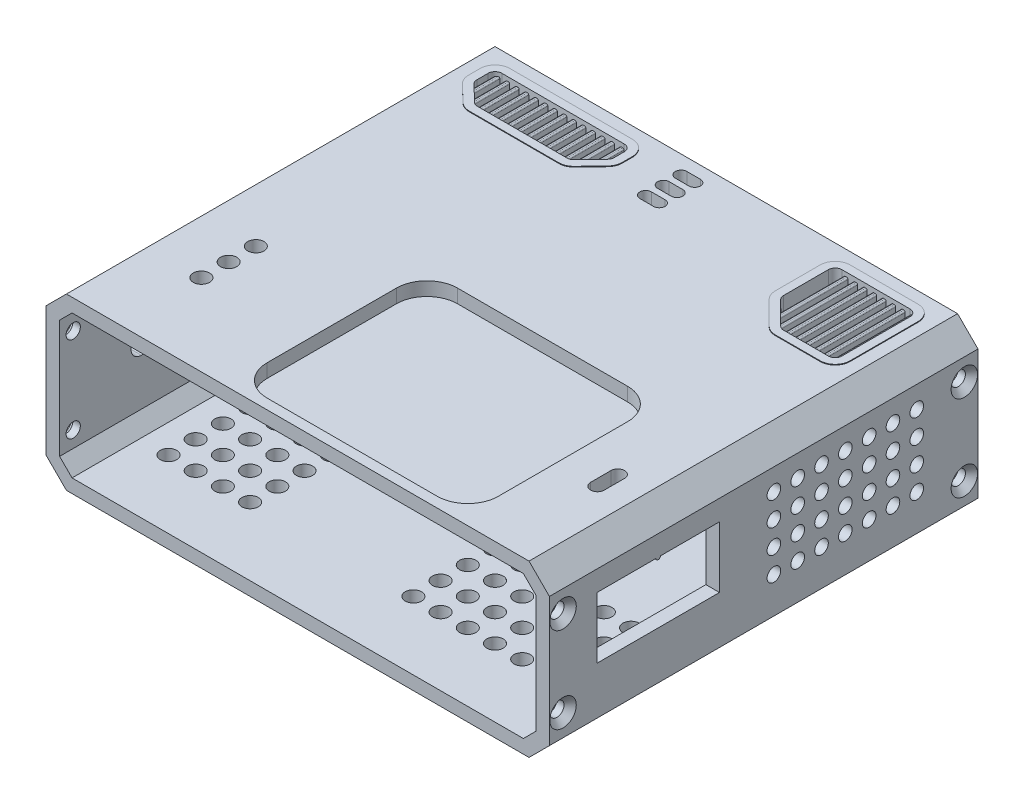
SolidWorks part; units mm, degrees
ref_plane "前视基准面" through (0, 0, 0) normal (0, 0, 1) x (1, 0, 0)
ref_plane "上视基准面" through (0, 0, 0) normal (0, 1, 0) x (1, 0, 0)
ref_plane "右视基准面" through (0, 0, 0) normal (1, 0, 0) x (0, 0, -1)
other "Configuration Table"
sketch "草图1" plane through (0, 0, 0) normal (0, 1, 0) x (1, 0, 0)
  line L1 (-36.9634, 47.435) -> (37.0366, 47.435)
  line L2 (-36.9634, 47.435) -> (-36.9634, -15.565)
  line L3 (-36.9634, -15.565) -> (37.0366, -15.565)
  line L4 (37.0366, 47.435) -> (37.0366, -15.565)
  dimension "D1" = 63
  dimension "D2" = 74
extrude "凸台-拉伸1" add sketch "草图1" along normal blind 25
chamfer "倒角1" distance 3 angle 45 4 edges at (37.0366, 0, -15.935) (-36.9634, 0, -15.935) (-36.9634, 25, -15.935) (37.0366, 25, -15.935)
sketch "草图2" plane through (0, 0, 15.565) normal (0, 0, 1) x (1, 0, 0)
  line L8 (-33.135, 2) -> (33.2082, 2)
  line L9 (35.0366, 3.8284) -> (35.0366, 21.1716)
  line L10 (33.2082, 23) -> (-33.135, 23)
  line L11 (-34.9634, 21.1716) -> (-34.9634, 3.8284)
  line L12 (-33.135, 2) -> (33.2082, 2)
  line L13 (35.0366, 3.8284) -> (35.0366, 21.1716)
  line L14 (33.2082, 23) -> (-33.135, 23)
  line L15 (-34.9634, 21.1716) -> (-34.9634, 3.8284)
  line L16 (33.2082, 2) -> (35.0366, 3.8284)
  line L17 (33.2082, 2) -> (35.0366, 3.8284)
  line L18 (35.0366, 21.1716) -> (33.2082, 23)
  line L19 (35.0366, 21.1716) -> (33.2082, 23)
  line L20 (-33.135, 23) -> (-34.9634, 21.1716)
  line L21 (-33.135, 23) -> (-34.9634, 21.1716)
  line L22 (-34.9634, 3.8284) -> (-33.135, 2)
  line L23 (-34.9634, 3.8284) -> (-33.135, 2)
  dimension "D1" = 2
extrude "切除-拉伸1" cut sketch "草图2" against normal through all
sketch "草图4" plane through (0, 25, 0) normal (0, 1, 0) x (1, 0, 0)
  line L0 (34.0366, 47.435) -> (-33.9634, 47.435) construction
  line L1 (-5.9634, 13.935) -> (19.0366, 13.935)
  line L2 (-10.4634, 9.435) -> (-10.4634, -9.565)
  line L3 (-5.9634, -14.065) -> (19.0366, -14.065)
  line L4 (23.5366, 9.435) -> (23.5366, -9.565)
  line L5 (-33.9634, -15.565) -> (34.0366, -15.565) construction
  line L7 (37.0366, 47.435) -> (37.0366, -15.565) construction
  arc A0 (19.0366, -14.065) -> (23.5366, -9.565) centre (19.0366, -9.565) ccw
  arc A1 (19.0366, 13.935) -> (23.5366, 9.435) centre (19.0366, 9.435) cw
  arc A2 (-10.4634, -9.565) -> (-5.9634, -14.065) centre (-5.9634, -9.565) ccw
  arc A3 (-5.9634, 13.935) -> (-10.4634, 9.435) centre (-5.9634, 9.435) ccw
  point P14 (23.5366, -14.065)
  point P17 (23.5366, 13.935)
  point P22 (-10.4634, 13.935)
  dimension "D5" = 4.5
  dimension "D1" = 34
  dimension "D2" = 1.5
  dimension "D3" = 33.5
  dimension "D4" = 13.5
extrude "切除-拉伸2" cut sketch "草图4" against normal up to next
sketch "草图5" plane through (0, 25, 0) normal (0, 1, 0) x (1, 0, 0)
  line L0 (-36.9634, 0.435) -> (-43.9993, 0.435) construction
  circle A0 centre (-26.1174, 0.435) radius 1.2
  circle A1 centre (-26.1174, 4.435) radius 1.2
  circle A2 centre (-26.1174, -3.565) radius 1.2
  dimension "D3" = 2.4
  dimension "D1" = 4
  dimension "D2" = 4
extrude "切除-拉伸3" cut sketch "草图5" against normal up to next
sketch "草图6" plane through (37.0366, 0, 0) normal (1, 0, 0) x (0, 0, -1)
  line L0 (-15.565, 22) -> (-15.565, 3) construction
  line L1 (-15.565, 3) -> (47.435, 3) construction
  line L2 (47.435, 22) -> (47.435, 3) construction
  line L3 (47.435, 22) -> (-15.565, 22) construction
  circle A0 centre (-13.565, 18.8) radius 1.05
  circle A1 centre (-13.565, 6.2) radius 1.05
  circle A2 centre (45.435, 6.2) radius 1.05
  circle A3 centre (45.435, 18.8) radius 1.05
  dimension "D1" = 2.1
  dimension "D2" = 2
  dimension "D3" = 3.2
  dimension "D4" = 2
  dimension "D5" = 3.2
extrude "切除-拉伸4" cut sketch "草图6" against normal through all
chamfer "倒角2" distance 0.9 angle 45 8 edges at (37.0366, 18.8, -46.485) (37.0366, 6.2, -46.485) (37.0366, 18.8, 12.515) (37.0366, 6.2, 12.515) (-36.9634, 6.2, -46.485) (-36.9634, 18.8, -46.485) (-36.9634, 6.2, 12.515) (-36.9634, 18.8, 12.515)
sketch "草图7" plane through (0, 25, 0) normal (0, 1, 0) x (1, 0, 0)
  line L0 (34.0366, 0.435) -> (47.8552, 0.435) construction
  line L2 (29.5366, 1.9891) -> (29.5366, -1.0109) construction
  line L3 (30.5366, 1.9891) -> (30.5366, -1.0109)
  line L4 (28.5366, 1.9891) -> (28.5366, -1.0109)
  line L5 (37.0366, 47.435) -> (37.0366, -15.565) construction
  arc A0 (30.5366, 1.9891) -> (28.5366, 1.9891) centre (29.5366, 1.9891) ccw
  arc A1 (28.5366, -1.0109) -> (30.5366, -1.0109) centre (29.5366, -1.0109) ccw
  point P3 (29.5366, 0.4891)
  dimension "D3" = 1
  dimension "D1" = 7.5
  dimension "D2" = 3
extrude "切除-拉伸5" cut sketch "草图7" against normal up to next
sketch "草图8" plane through (-36.9634, 0, 0) normal (-1, 0, 0) x (0, 0, 1)
  line L0 (-2.435, 11.4156) -> (-2.435, -8.1835) construction
  line L1 (-8.435, 12.2) -> (3.565, 12.2) construction
  line L2 (-8.435, 13.7) -> (3.565, 13.7)
  line L3 (-8.435, 10.7) -> (3.565, 10.7)
  line L5 (-47.435, 25) -> (15.565, 25) construction
  line L6 (15.565, 22) -> (15.565, 3) construction
  arc A0 (-8.435, 13.7) -> (-8.435, 10.7) centre (-8.435, 12.2) ccw
  arc A1 (3.565, 10.7) -> (3.565, 13.7) centre (3.565, 12.2) ccw
  point P3 (-2.435, 12.2)
  dimension "D4" = 1.5
  dimension "D1" = 18
  dimension "D2" = 12
  dimension "D3" = 12.8
extrude "切除-拉伸6" cut sketch "草图8" against normal up to next
sketch "草图9" plane through (-36.9634, 0, 0) normal (-1, 0, 0) x (0, 0, 1)
  line L1 (-7.435, 7) -> (-3.435, 7)
  line L2 (-7.435, 7) -> (-7.435, 5)
  line L3 (-7.435, 5) -> (-3.435, 5)
  line L4 (-3.435, 7) -> (-3.435, 5)
  line L5 (-47.435, 25) -> (15.565, 25) construction
  line L6 (15.565, 22) -> (15.565, 3) construction
  dimension "D1" = 19
  dimension "D2" = 2
  dimension "D3" = 18
  dimension "D4" = 4
extrude "切除-拉伸7" cut sketch "草图9" against normal up to next
fillet "圆角1" radius 1 4 edges at (-35.9634, 5, -3.435) (-35.9634, 7, -3.435) (-35.9634, 7, -7.435) (-35.9634, 5, -7.435)
sketch "草图10" plane through (-36.9634, 0, 0) normal (-1, 0, 0) x (0, 0, 1)
  line L0 (-47.435, 25) -> (15.565, 25) construction
  line L3 (15.565, 22) -> (15.565, 3) construction
  circle A0 centre (6.465, 19) radius 1
  circle A1 centre (3.265, 19) radius 1
  circle A2 centre (0.065, 19) radius 1
  circle A3 centre (-3.135, 19) radius 1
  circle A4 centre (-6.335, 19) radius 1
  circle A5 centre (3.265, 15.8) radius 1
  circle A6 centre (0.065, 15.8) radius 1
  circle A7 centre (-3.135, 15.8) radius 1
  circle A8 centre (-6.335, 15.8) radius 1
  circle A9 centre (6.465, 15.8) radius 1
  circle A10 centre (-9.535, 19) radius 1
  circle A11 centre (-12.735, 19) radius 1
  circle A12 centre (-15.935, 19) radius 1
  circle A13 centre (-19.135, 19) radius 1
  circle A14 centre (-22.335, 19) radius 1
  circle A15 centre (-25.535, 19) radius 1
  circle A16 centre (-28.735, 19) radius 1
  circle A17 centre (-31.935, 19) radius 1
  circle A18 centre (-35.135, 19) radius 1
  circle A19 centre (-38.335, 19) radius 1
  circle A20 centre (-9.535, 15.8) radius 1
  circle A21 centre (-12.735, 15.8) radius 1
  circle A22 centre (-15.935, 15.8) radius 1
  circle A23 centre (-19.135, 15.8) radius 1
  circle A24 centre (-22.335, 15.8) radius 1
  circle A25 centre (-25.535, 15.8) radius 1
  circle A26 centre (-28.735, 15.8) radius 1
  circle A27 centre (-31.935, 15.8) radius 1
  circle A28 centre (-35.135, 15.8) radius 1
  circle A29 centre (-38.335, 15.8) radius 1
  dimension "D3" = 2
  dimension "D1" = 6
  dimension "D2" = 9.1
  dimension "D4" = 15
  dimension "D5" = 2
extrude "切除-拉伸8" cut sketch "草图10" against normal up to next (2 mm away)
sketch "草图11" plane through (37.0366, 0, 0) normal (1, 0, 0) x (0, 0, -1)
  line L1 (-8.565, 19) -> (9.435, 19)
  line L3 (-8.565, 10) -> (9.435, 10)
  line L5 (-15.565, 25) -> (47.435, 25) construction
  line L18 (-8.565, 19) -> (-8.565, 10)
  line L19 (9.435, 19) -> (9.435, 10)
  line L20 (-15.565, 22) -> (-15.565, 3) construction
  dimension "D1" = 18
  dimension "D2" = 7
  dimension "D3" = 6
  dimension "D4" = 9
extrude "切除-拉伸9" cut sketch "草图11" against normal up to next
sketch "草图12" plane through (0, 0, -47.435) normal (0, 0, -1) x (-1, 0, 0)
  line L0 (-33.2082, 23) -> (33.135, 23) construction
  line L1 (24.9634, 23) -> (26.9634, 23)
  line L2 (24.9634, 23) -> (24.9634, 15.7)
  line L3 (24.9634, 15.7) -> (26.9634, 15.7)
  line L4 (26.9634, 23) -> (26.9634, 15.7)
  line L5 (36.9634, 22) -> (36.9634, 3) construction
  line L6 (-17.0366, 23) -> (-15.0366, 23)
  line L7 (-17.0366, 23) -> (-17.0366, 15.7)
  line L8 (-17.0366, 15.7) -> (-15.0366, 15.7)
  line L9 (-15.0366, 23) -> (-15.0366, 15.7)
  line L10 (-37.0366, 22) -> (-37.0366, 3) construction
  dimension "D1" = 2
  dimension "D2" = 10
  dimension "D3" = 20
  dimension "D4" = 7.3
extrude "凸台-拉伸2" add sketch "草图12" against normal blind 20
chamfer "倒角3" distance 6 angle 45 2 edges at (16.0366, 15.7, -27.435) (-25.9634, 15.7, -27.435)
sketch "草图13" plane through (0, 0, -47.435) normal (0, 0, -1) x (-1, 0, 0)
  line L0 (24.9634, 15.7) -> (26.9634, 15.7) construction
  line L1 (-33.2082, 23) -> (33.135, 23)
  line L2 (-33.2082, 23) -> (-33.2082, 15.7)
  line L3 (-33.2082, 15.7) -> (33.135, 15.7)
  line L4 (33.135, 23) -> (33.135, 15.7)
extrude "切除-拉伸10" cut sketch "草图13" against normal blind 10
sketch "草图15" plane through (37.0366, 0, 0) normal (1, 0, 0) x (0, 0, -1)
  line L0 (-15.565, 25) -> (47.435, 25) construction
  line L1 (47.435, 25) -> (47.435, 22) construction
  circle A0 centre (38.435, 18.8) radius 1
  circle A1 centre (34.935, 18.8) radius 1
  circle A2 centre (31.435, 18.8) radius 1
  circle A3 centre (27.935, 18.8) radius 1
  circle A4 centre (24.435, 18.8) radius 1
  circle A5 centre (20.935, 18.8) radius 1
  circle A6 centre (17.435, 18.8) radius 1
  circle A7 centre (34.935, 15.3) radius 1
  circle A8 centre (31.435, 15.3) radius 1
  circle A9 centre (27.935, 15.3) radius 1
  circle A10 centre (24.435, 15.3) radius 1
  circle A11 centre (20.935, 15.3) radius 1
  circle A12 centre (17.435, 15.3) radius 1
  circle A13 centre (34.935, 11.8) radius 1
  circle A14 centre (31.435, 11.8) radius 1
  circle A15 centre (27.935, 11.8) radius 1
  circle A16 centre (24.435, 11.8) radius 1
  circle A17 centre (20.935, 11.8) radius 1
  circle A18 centre (17.435, 11.8) radius 1
  circle A19 centre (34.935, 8.3) radius 1
  circle A20 centre (31.435, 8.3) radius 1
  circle A21 centre (27.935, 8.3) radius 1
  circle A22 centre (24.435, 8.3) radius 1
  circle A23 centre (20.935, 8.3) radius 1
  circle A24 centre (17.435, 8.3) radius 1
  circle A25 centre (38.435, 15.3) radius 1
  circle A26 centre (38.435, 11.8) radius 1
  circle A27 centre (38.435, 8.3) radius 1
  dimension "D1" = 2
  dimension "D4" = 7
  dimension "D2" = 6.2
  dimension "D3" = 9
  dimension "D5" = 4
extrude "切除-拉伸12" cut sketch "草图15" against normal up to next (2 mm away)
sketch "草图16" plane through (0, 23, 0) normal (0, -1, 0) x (1, 0, 0)
  line L1 (-28.599, -18.535) -> (-26.599, -18.535)
  line L2 (-28.599, -18.535) -> (-28.599, -15.535)
  line L3 (-28.599, -15.535) -> (-26.599, -15.535)
  line L4 (-26.599, -18.535) -> (-26.599, -15.535)
  line L5 (33.2082, -47.435) -> (-33.135, -47.435) construction
  line L6 (26.6682, -18.535) -> (28.6682, -18.535)
  line L7 (26.6682, -18.535) -> (26.6682, -15.535)
  line L8 (26.6682, -15.535) -> (28.6682, -15.535)
  line L9 (28.6682, -18.535) -> (28.6682, -15.535)
  line L10 (-33.135, -47.435) -> (-33.135, 15.565) construction
  line L11 (33.2082, -47.435) -> (33.2082, 15.565) construction
  point P4 (0, 0)
  point P10 (0, 0)
  point P11 (0, 0)
  point P12 (0, 0)
  point P18 (0, 0)
  dimension "D1" = 31.9
  dimension "D2" = 4.5359
  dimension "D3" = 4.54
  dimension "D4" = 2
  dimension "D5" = 3
extrude "凸台-拉伸3" add sketch "草图16" along normal blind 4
sketch "草图18" plane through (0, 2, 0) normal (0, 1, 0) x (1, 0, 0)
  line L0 (33.6224, 49.435) -> (-33.5492, 49.435) construction
  line L1 (37.0366, -15.565) -> (37.0366, 47.435) construction
  line L2 (37.0366, 43.485) -> (37.0366, 47.385) construction
  circle A0 centre (27.0366, 6.435) radius 1.2
  circle A1 centre (23.0366, 6.435) radius 1.2
  circle A2 centre (19.0366, 6.435) radius 1.2
  circle A3 centre (15.0366, 6.435) radius 1.2
  circle A4 centre (11.0366, 6.435) radius 1.2
  circle A5 centre (7.0366, 6.435) radius 1.2
  circle A6 centre (23.0366, 2.435) radius 1.2
  circle A7 centre (19.0366, 2.435) radius 1.2
  circle A8 centre (15.0366, 2.435) radius 1.2
  circle A9 centre (11.0366, 2.435) radius 1.2
  circle A10 centre (7.0366, 2.435) radius 1.2
  circle A11 centre (23.0366, -1.565) radius 1.2
  circle A12 centre (19.0366, -1.565) radius 1.2
  circle A13 centre (15.0366, -1.565) radius 1.2
  circle A14 centre (11.0366, -1.565) radius 1.2
  circle A15 centre (7.0366, -1.565) radius 1.2
  circle A16 centre (23.0366, -5.565) radius 1.2
  circle A17 centre (19.0366, -5.565) radius 1.2
  circle A18 centre (15.0366, -5.565) radius 1.2
  circle A19 centre (11.0366, -5.565) radius 1.2
  circle A20 centre (7.0366, -5.565) radius 1.2
  circle A26 centre (27.0366, 2.435) radius 1.2
  circle A27 centre (27.0366, -1.565) radius 1.2
  circle A28 centre (27.0366, -5.565) radius 1.2
  circle A30 centre (-16.9634, 6.435) radius 1.2
  circle A31 centre (-20.9634, 6.435) radius 1.2
  circle A32 centre (-24.9634, 6.435) radius 1.2
  circle A33 centre (-20.9634, 2.435) radius 1.2
  circle A34 centre (-24.9634, 2.435) radius 1.2
  circle A35 centre (-20.9634, -1.565) radius 1.2
  circle A36 centre (-24.9634, -1.565) radius 1.2
  circle A37 centre (-20.9634, -5.565) radius 1.2
  circle A38 centre (-24.9634, -5.565) radius 1.2
  circle A41 centre (-16.9634, 2.435) radius 1.2
  circle A42 centre (-16.9634, -1.565) radius 1.2
  circle A43 centre (-16.9634, -5.565) radius 1.2
  circle A45 centre (-28.9634, 6.435) radius 1.2
  circle A46 centre (-28.9634, 2.435) radius 1.2
  circle A47 centre (-28.9634, -1.565) radius 1.2
  circle A48 centre (-28.9634, -5.565) radius 1.2
  dimension "D3" = 2.4
  dimension "D1" = 43
  dimension "D2" = 10
  dimension "D6" = 54
  dimension "D4" = 6
  dimension "D5" = 4
  dimension "D7" = 4
  dimension "D8" = 4
extrude "切除-拉伸13" cut sketch "草图18" against normal through all
sketch "草图19" plane through (37.0366, 0, 0) normal (1, 0, 0) x (0, 0, -1)
  line L0 (9.435, 19) -> (-8.565, 19) construction
  circle A0 centre (0.435, 19) radius 0.325
  dimension "D1" = 0.65
extrude "凸台-拉伸4" add sketch "草图19" against normal blind 2
sketch "草图21" plane through (0, 25, 0) normal (0, 1, 0) x (1, 0, 0)
  line L1 (31.0366, 43.435) -> (31.0366, 33.435)
  line L2 (30.0366, 32.435) -> (23.4508, 32.435)
  line L3 (22.7437, 32.7279) -> (19.3295, 36.1421)
  line L4 (19.0366, 36.8492) -> (19.0366, 43.435)
  line L5 (20.0366, 44.435) -> (30.0366, 44.435)
  line L6 (-11.9634, 44.435) -> (-29.9634, 44.435)
  line L7 (-30.9634, 43.435) -> (-30.9634, 41.7558)
  line L8 (-30.6564, 41.0349) -> (-28.2421, 38.7141)
  line L9 (-27.5491, 38.435) -> (-14.3776, 38.435)
  line L10 (-13.6567, 38.742) -> (-11.2425, 41.2535)
  line L11 (-10.9634, 41.9465) -> (-10.9634, 43.435)
  line L12 (34.0366, 47.435) -> (-33.9634, 47.435) construction
  line L13 (34.0366, -15.565) -> (34.0366, 47.435) construction
  line L14 (-33.9634, 47.435) -> (-33.9634, -15.565) construction
  line L26 (-11.9634, 45.635) -> (-29.9634, 45.635)
  line L27 (-32.1634, 43.435) -> (-32.1634, 41.7558)
  line L28 (-31.488, 40.1697) -> (-29.0737, 37.849)
  line L29 (-27.5491, 37.235) -> (-14.3776, 37.235)
  line L30 (-12.7916, 37.9104) -> (-10.3773, 40.4219)
  line L31 (-9.7634, 41.9465) -> (-9.7634, 43.435)
  line L32 (32.2366, 43.435) -> (32.2366, 33.435)
  line L33 (30.0366, 31.235) -> (23.4508, 31.235)
  line L34 (21.8952, 31.8794) -> (18.481, 35.2936)
  line L35 (17.8366, 36.8492) -> (17.8366, 43.435)
  line L36 (20.0366, 45.635) -> (30.0366, 45.635)
  arc A0 (31.0366, 43.435) -> (30.0366, 44.435) centre (30.0366, 43.435) ccw
  arc A1 (31.0366, 33.435) -> (30.0366, 32.435) centre (30.0366, 33.435) cw
  arc A2 (23.4508, 32.435) -> (22.7437, 32.7279) centre (23.4508, 33.435) cw
  arc A3 (19.3295, 36.1421) -> (19.0366, 36.8492) centre (20.0366, 36.8492) cw
  arc A4 (19.0366, 43.435) -> (20.0366, 44.435) centre (20.0366, 43.435) cw
  arc A5 (-14.3776, 38.435) -> (-13.6567, 38.742) centre (-14.3776, 39.435) ccw
  arc A6 (-28.2421, 38.7141) -> (-27.5491, 38.435) centre (-27.5491, 39.435) ccw
  arc A7 (-30.9634, 41.7558) -> (-30.6564, 41.0349) centre (-29.9634, 41.7558) ccw
  arc A8 (-11.2425, 41.2535) -> (-10.9634, 41.9465) centre (-11.9634, 41.9465) ccw
  arc A9 (-10.9634, 43.435) -> (-11.9634, 44.435) centre (-11.9634, 43.435) ccw
  arc A10 (-29.9634, 44.435) -> (-30.9634, 43.435) centre (-29.9634, 43.435) ccw
  arc A11 (-29.9634, 45.635) -> (-32.1634, 43.435) centre (-29.9634, 43.435) ccw
  arc A12 (-32.1634, 41.7558) -> (-31.488, 40.1697) centre (-29.9634, 41.7558) ccw
  arc A13 (-29.0737, 37.849) -> (-27.5491, 37.235) centre (-27.5491, 39.435) ccw
  arc A14 (-14.3776, 37.235) -> (-12.7916, 37.9104) centre (-14.3776, 39.435) ccw
  arc A15 (-10.3773, 40.4219) -> (-9.7634, 41.9465) centre (-11.9634, 41.9465) ccw
  arc A16 (-9.7634, 43.435) -> (-11.9634, 45.635) centre (-11.9634, 43.435) ccw
  arc A17 (32.2366, 33.435) -> (30.0366, 31.235) centre (30.0366, 33.435) cw
  arc A18 (23.4508, 31.235) -> (21.8952, 31.8794) centre (23.4508, 33.435) cw
  arc A19 (18.481, 35.2936) -> (17.8366, 36.8492) centre (20.0366, 36.8492) cw
  arc A20 (17.8366, 43.435) -> (20.0366, 45.635) centre (20.0366, 43.435) cw
  arc A21 (32.2366, 43.435) -> (30.0366, 45.635) centre (30.0366, 43.435) ccw
  point P4 (0, 0)
  point P12 (0, 0)
  point P13 (0, 0)
  point P14 (0, 0)
  point P21 (-20.9634, 38.435)
  point P22 (-20.9634, 44.435)
  point P25 (31.0366, 44.435)
  point P28 (31.0366, 32.435)
  point P31 (23.0366, 32.435)
  point P34 (19.0366, 36.435)
  point P37 (19.0366, 44.435)
  point P40 (-13.9518, 38.435)
  point P43 (-27.9518, 38.435)
  point P50 (-10.9634, 44.435)
  point P53 (-30.9634, 44.435)
  dimension "D11" = 1
  dimension "D1" = 3
  dimension "D2" = 3
  dimension "D3" = 3
  dimension "D4" = 20
  dimension "D5" = 12
  dimension "D6" = 12
  dimension "D7" = 8
  dimension "D8" = 8
  dimension "D9" = 14
  dimension "D10" = 6
  dimension "D12" = 1.2
  dimension "D13" = 1.2
extrude "凸台-拉伸5" add sketch "草图21" along normal blind 0.1
sketch "草图22" plane through (0, 25, 0) normal (0, 1, 0) x (1, 0, 0)
  line L22 (-13.6567, 38.742) -> (-11.2425, 41.2535) construction
  line L23 (-10.9634, 41.9465) -> (-10.9634, 43.435) construction
  line L24 (-11.9634, 44.435) -> (-29.9634, 44.435) construction
  line L25 (-30.9634, 43.435) -> (-30.9634, 41.7558) construction
  line L26 (-30.6564, 41.0349) -> (-28.2421, 38.7141) construction
  line L27 (-27.5491, 38.435) -> (-14.3776, 38.435) construction
  line L28 (30.0366, 44.435) -> (20.0366, 44.435) construction
  line L29 (19.0366, 43.435) -> (19.0366, 36.8492) construction
  line L30 (19.3295, 36.1421) -> (22.7437, 32.7279) construction
  line L31 (23.4508, 32.435) -> (30.0366, 32.435) construction
  line L32 (31.0366, 33.435) -> (31.0366, 43.435) construction
  line L33 (-13.6567, 38.742) -> (-11.2425, 41.2535)
  line L34 (-10.9634, 41.9465) -> (-10.9634, 43.435)
  line L35 (-11.9634, 44.435) -> (-29.9634, 44.435)
  line L36 (-30.9634, 43.435) -> (-30.9634, 41.7558)
  line L37 (-30.6564, 41.0349) -> (-28.2421, 38.7141)
  line L38 (-27.5491, 38.435) -> (-14.3776, 38.435)
  line L39 (30.0366, 44.435) -> (20.0366, 44.435)
  line L40 (19.0366, 43.435) -> (19.0366, 36.8492)
  line L41 (19.3295, 36.1421) -> (22.7437, 32.7279)
  line L42 (23.4508, 32.435) -> (30.0366, 32.435)
  line L43 (31.0366, 33.435) -> (31.0366, 43.435)
  arc A0 (-14.3776, 38.435) -> (-13.6567, 38.742) centre (-14.3776, 39.435) ccw construction
  arc A1 (-11.2425, 41.2535) -> (-10.9634, 41.9465) centre (-11.9634, 41.9465) ccw construction
  arc A2 (-10.9634, 43.435) -> (-11.9634, 44.435) centre (-11.9634, 43.435) ccw construction
  arc A3 (-29.9634, 44.435) -> (-30.9634, 43.435) centre (-29.9634, 43.435) ccw construction
  arc A4 (-30.9634, 41.7558) -> (-30.6564, 41.0349) centre (-29.9634, 41.7558) ccw construction
  arc A5 (-28.2421, 38.7141) -> (-27.5491, 38.435) centre (-27.5491, 39.435) ccw construction
  arc A6 (31.0366, 43.435) -> (30.0366, 44.435) centre (30.0366, 43.435) ccw construction
  arc A7 (20.0366, 44.435) -> (19.0366, 43.435) centre (20.0366, 43.435) ccw construction
  arc A8 (19.0366, 36.8492) -> (19.3295, 36.1421) centre (20.0366, 36.8492) ccw construction
  arc A9 (22.7437, 32.7279) -> (23.4508, 32.435) centre (23.4508, 33.435) ccw construction
  arc A10 (30.0366, 32.435) -> (31.0366, 33.435) centre (30.0366, 33.435) ccw construction
  arc A11 (-14.3776, 38.435) -> (-13.6567, 38.742) centre (-14.3776, 39.435) ccw
  arc A12 (-11.2425, 41.2535) -> (-10.9634, 41.9465) centre (-11.9634, 41.9465) ccw
  arc A13 (-10.9634, 43.435) -> (-11.9634, 44.435) centre (-11.9634, 43.435) ccw
  arc A14 (-29.9634, 44.435) -> (-30.9634, 43.435) centre (-29.9634, 43.435) ccw
  arc A15 (-30.9634, 41.7558) -> (-30.6564, 41.0349) centre (-29.9634, 41.7558) ccw
  arc A16 (-28.2421, 38.7141) -> (-27.5491, 38.435) centre (-27.5491, 39.435) ccw
  arc A17 (31.0366, 43.435) -> (30.0366, 44.435) centre (30.0366, 43.435) ccw
  arc A18 (20.0366, 44.435) -> (19.0366, 43.435) centre (20.0366, 43.435) ccw
  arc A19 (19.0366, 36.8492) -> (19.3295, 36.1421) centre (20.0366, 36.8492) ccw
  arc A20 (22.7437, 32.7279) -> (23.4508, 32.435) centre (23.4508, 33.435) ccw
  arc A21 (30.0366, 32.435) -> (31.0366, 33.435) centre (30.0366, 33.435) ccw
extrude "切除-拉伸15" cut sketch "草图22" against normal blind 2
ref_plane "基准面1" through (0, 24.5, 0) normal (0, 1, 0) x (1, 0, 0)
sketch "草图23" plane through (0, 24.5, 0) normal (0, 1, 0) x (1, 0, 0)
  line L0 (28.7385, 45.7265) -> (29.3385, 45.7265)
  line L1 (30.1385, 45.7265) -> (30.7385, 45.7265)
  line L2 (30.1385, 45.7265) -> (30.1385, 32.4528)
  line L3 (30.1385, 32.4528) -> (30.7385, 32.4528)
  line L4 (30.7385, 45.7265) -> (30.7385, 32.4528)
  line L5 (28.7385, 45.7265) -> (28.7385, 32.4528)
  line L6 (28.7385, 32.4528) -> (29.3385, 32.4528)
  line L7 (29.3385, 45.7265) -> (29.3385, 32.4528)
  line L8 (27.3385, 45.7265) -> (27.9385, 45.7265)
  line L9 (27.3385, 45.7265) -> (27.3385, 32.4528)
  line L10 (27.3385, 32.4528) -> (27.9385, 32.4528)
  line L11 (27.9385, 45.7265) -> (27.9385, 32.4528)
  line L12 (25.9385, 45.7265) -> (26.5385, 45.7265)
  line L13 (25.9385, 45.7265) -> (25.9385, 32.4528)
  line L14 (25.9385, 32.4528) -> (26.5385, 32.4528)
  line L15 (26.5385, 45.7265) -> (26.5385, 32.4528)
  line L16 (24.5385, 45.7265) -> (25.1385, 45.7265)
  line L17 (24.5385, 45.7265) -> (24.5385, 32.4528)
  line L18 (24.5385, 32.4528) -> (25.1385, 32.4528)
  line L19 (25.1385, 45.7265) -> (25.1385, 32.4528)
  line L20 (23.1385, 45.7265) -> (23.7385, 45.7265)
  line L21 (23.1385, 45.7265) -> (23.1385, 32.4528)
  line L22 (23.1385, 32.4528) -> (23.7385, 32.4528)
  line L23 (23.7385, 45.7265) -> (23.7385, 32.4528)
  line L24 (21.7385, 45.7265) -> (22.3385, 45.7265)
  line L25 (21.7385, 45.7265) -> (21.7385, 32.4528)
  line L26 (21.7385, 32.4528) -> (22.3385, 32.4528)
  line L27 (22.3385, 45.7265) -> (22.3385, 32.4528)
  line L28 (20.3385, 45.7265) -> (20.9385, 45.7265)
  line L29 (20.3385, 45.7265) -> (20.3385, 32.4528)
  line L30 (20.3385, 32.4528) -> (20.9385, 32.4528)
  line L31 (20.9385, 45.7265) -> (20.9385, 32.4528)
  line L32 (-13.9994, 46.4523) -> (-13.3994, 46.4523)
  line L33 (-12.5994, 46.4523) -> (-11.9994, 46.4523)
  line L34 (-12.5994, 46.4523) -> (-12.5994, 37.7287)
  line L35 (-12.5994, 37.7287) -> (-11.9994, 37.7287)
  line L36 (-11.9994, 46.4523) -> (-11.9994, 37.7287)
  line L37 (-13.9994, 46.4523) -> (-13.9994, 37.7287)
  line L38 (-13.9994, 37.7287) -> (-13.3994, 37.7287)
  line L39 (-13.3994, 46.4523) -> (-13.3994, 37.7287)
  line L40 (-15.3994, 46.4523) -> (-14.7994, 46.4523)
  line L41 (-15.3994, 46.4523) -> (-15.3994, 37.7287)
  line L42 (-15.3994, 37.7287) -> (-14.7994, 37.7287)
  line L43 (-14.7994, 46.4523) -> (-14.7994, 37.7287)
  line L44 (-16.7994, 46.4523) -> (-16.1994, 46.4523)
  line L45 (-16.7994, 46.4523) -> (-16.7994, 37.7287)
  line L46 (-16.7994, 37.7287) -> (-16.1994, 37.7287)
  line L47 (-16.1994, 46.4523) -> (-16.1994, 37.7287)
  line L48 (-18.1994, 46.4523) -> (-17.5994, 46.4523)
  line L49 (-18.1994, 46.4523) -> (-18.1994, 37.7287)
  line L50 (-18.1994, 37.7287) -> (-17.5994, 37.7287)
  line L51 (-17.5994, 46.4523) -> (-17.5994, 37.7287)
  line L52 (-19.5994, 46.4523) -> (-18.9994, 46.4523)
  line L53 (-19.5994, 46.4523) -> (-19.5994, 37.7287)
  line L54 (-19.5994, 37.7287) -> (-18.9994, 37.7287)
  line L55 (-18.9994, 46.4523) -> (-18.9994, 37.7287)
  line L56 (-20.9994, 46.4523) -> (-20.3994, 46.4523)
  line L57 (-20.9994, 46.4523) -> (-20.9994, 37.7287)
  line L58 (-20.9994, 37.7287) -> (-20.3994, 37.7287)
  line L59 (-20.3994, 46.4523) -> (-20.3994, 37.7287)
  line L60 (-22.3994, 46.4523) -> (-21.7994, 46.4523)
  line L61 (-22.3994, 46.4523) -> (-22.3994, 37.7287)
  line L62 (-22.3994, 37.7287) -> (-21.7994, 37.7287)
  line L63 (-21.7994, 46.4523) -> (-21.7994, 37.7287)
  line L64 (-23.7994, 46.4523) -> (-23.1994, 46.4523)
  line L65 (-23.7994, 46.4523) -> (-23.7994, 37.7287)
  line L66 (-23.7994, 37.7287) -> (-23.1994, 37.7287)
  line L67 (-23.1994, 46.4523) -> (-23.1994, 37.7287)
  line L68 (-25.1994, 46.4523) -> (-24.5994, 46.4523)
  line L69 (-25.1994, 46.4523) -> (-25.1994, 37.7287)
  line L70 (-25.1994, 37.7287) -> (-24.5994, 37.7287)
  line L71 (-24.5994, 46.4523) -> (-24.5994, 37.7287)
  line L72 (-26.5994, 46.4523) -> (-25.9994, 46.4523)
  line L73 (-26.5994, 46.4523) -> (-26.5994, 37.7287)
  line L74 (-26.5994, 37.7287) -> (-25.9994, 37.7287)
  line L75 (-25.9994, 46.4523) -> (-25.9994, 37.7287)
  line L76 (-27.9994, 46.4523) -> (-27.3994, 46.4523)
  line L77 (-27.9994, 46.4523) -> (-27.9994, 37.7287)
  line L78 (-27.9994, 37.7287) -> (-27.3994, 37.7287)
  line L79 (-27.3994, 46.4523) -> (-27.3994, 37.7287)
  line L80 (-29.3994, 46.4523) -> (-28.7994, 46.4523)
  line L81 (-29.3994, 46.4523) -> (-29.3994, 37.7287)
  line L82 (-29.3994, 37.7287) -> (-28.7994, 37.7287)
  line L83 (-28.7994, 46.4523) -> (-28.7994, 37.7287)
  line L84 (-30.7994, 46.4523) -> (-30.1994, 46.4523)
  line L85 (-30.7994, 46.4523) -> (-30.7994, 37.7287)
  line L86 (-30.7994, 37.7287) -> (-30.1994, 37.7287)
  line L87 (-30.1994, 46.4523) -> (-30.1994, 37.7287)
  dimension "D1" = 0.6
  dimension "D2" = 8
  dimension "D3" = 14
extrude "凸台-拉伸6" add sketch "草图23" against normal blind 1.5
fillet "圆角2" radius 0.2 44 edges at (-30.7994, 24.5, -42.5954) (-30.1994, 24.5, -42.5011) (-29.3994, 24.5, -42.1307) (-28.7994, 24.5, -41.8424) (-27.9994, 24.5, -41.4885) (-27.3994, 24.5, -41.435) (-26.5994, 24.5, -41.435) (-25.9994, 24.5, -41.435) (-25.1994, 24.5, -41.435) (-24.5994, 24.5, -41.435) (-23.7994, 24.5, -41.435) (-23.1994, 24.5, -41.435) (-22.3994, 24.5, -41.435) (-21.7994, 24.5, -41.435) (-20.9994, 24.5, -41.435) (-20.3994, 24.5, -41.435) (-19.5994, 24.5, -41.435) (-18.9994, 24.5, -41.435) (-18.1994, 24.5, -41.435) (-17.5994, 24.5, -41.435) (-16.7994, 24.5, -41.435) (-16.1994, 24.5, -41.435) (-15.3994, 24.5, -41.435) (-14.7994, 24.5, -41.435) (-13.9994, 24.5, -41.4722) (-13.3994, 24.5, -41.7224) (-12.5994, 24.5, -42.1385) (-11.9994, 24.5, -42.4506) (20.3385, 24.5, -39.7841) (20.9385, 24.5, -39.4841) (21.7385, 24.5, -39.0841) (22.3385, 24.5, -38.7841) (23.1385, 24.5, -38.46) (23.7385, 24.5, -38.4439) (24.5385, 24.5, -38.4439) (25.1385, 24.5, -38.4439) (25.9385, 24.5, -38.4439) (26.5385, 24.5, -38.4439) (27.3385, 24.5, -38.4439) (27.9385, 24.5, -38.4439) (28.7385, 24.5, -38.4439) (29.3385, 24.5, -38.4439) (30.1385, 24.5, -38.4413) (30.7385, 24.5, -38.435)
sketch "草图24" plane through (0, 25, 0) normal (0, 1, 0) x (1, 0, 0)
  line L0 (-3.9634, 44.785) -> (-1.9634, 44.785) construction
  line L1 (-3.9634, 45.635) -> (-1.9634, 45.635)
  line L2 (-3.9634, 43.935) -> (-1.9634, 43.935)
  line L3 (-11.9634, 45.635) -> (-29.9634, 45.635) construction
  line L4 (-33.9634, 47.435) -> (-33.9634, -15.565) construction
  line L5 (-3.9634, 42.185) -> (-1.9634, 42.185) construction
  line L6 (-3.9634, 43.035) -> (-1.9634, 43.035)
  line L7 (-3.9634, 41.335) -> (-1.9634, 41.335)
  line L8 (-3.9634, 39.585) -> (-1.9634, 39.585) construction
  line L9 (-3.9634, 40.435) -> (-1.9634, 40.435)
  line L10 (-3.9634, 38.735) -> (-1.9634, 38.735)
  arc A0 (-3.9634, 45.635) -> (-3.9634, 43.935) centre (-3.9634, 44.785) ccw
  arc A1 (-1.9634, 43.935) -> (-1.9634, 45.635) centre (-1.9634, 44.785) ccw
  arc A2 (-3.9634, 43.035) -> (-3.9634, 41.335) centre (-3.9634, 42.185) ccw
  arc A3 (-1.9634, 41.335) -> (-1.9634, 43.035) centre (-1.9634, 42.185) ccw
  arc A4 (-3.9634, 40.435) -> (-3.9634, 38.735) centre (-3.9634, 39.585) ccw
  arc A5 (-1.9634, 38.735) -> (-1.9634, 40.435) centre (-1.9634, 39.585) ccw
  point P2 (-2.9634, 44.785)
  point P14 (-2.9634, 42.185)
  point P21 (-2.9634, 39.585)
  dimension "D1" = 0.85
  dimension "D2" = 30
  dimension "D3" = 2
  dimension "D4" = 3
extrude "切除-拉伸16" cut sketch "草图24" against normal up to next
